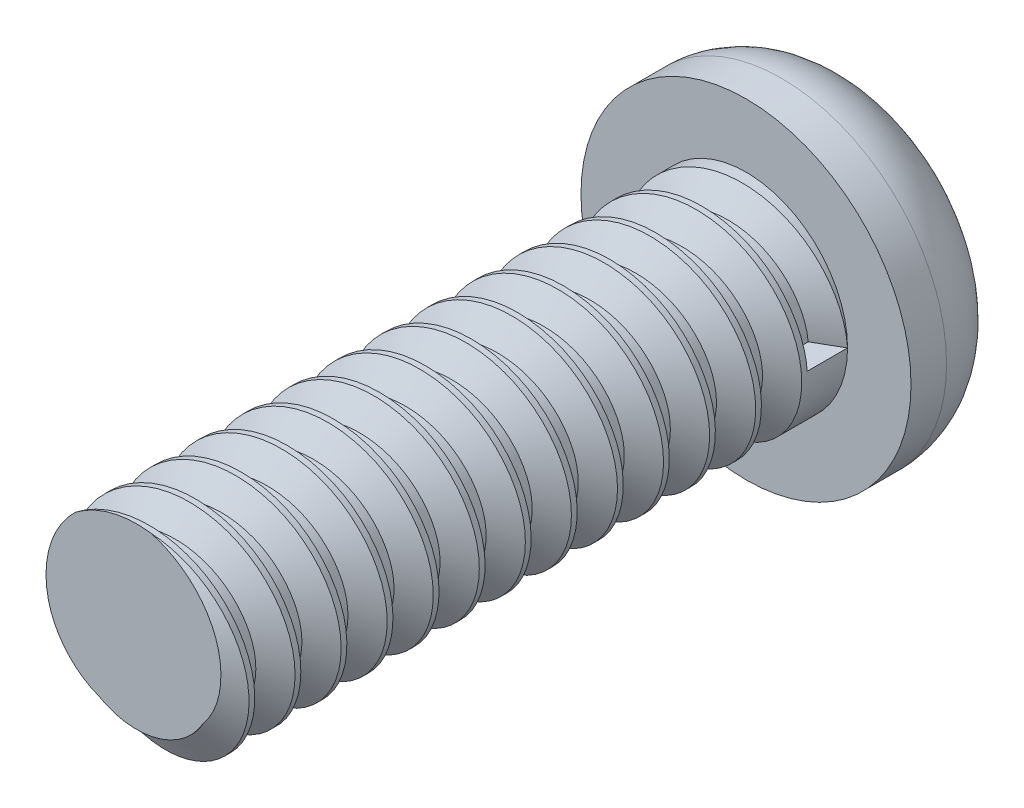
SolidWorks part; units mm, degrees
ref_plane "前视基准面" through (0, 0, 0) normal (0, 0, 1) x (1, 0, 0)
ref_plane "上视基准面" through (0, 0, 0) normal (0, 1, 0) x (1, 0, 0)
ref_plane "右视基准面" through (0, 0, 0) normal (1, 0, 0) x (0, 0, -1)
sketch "草图1" plane through (0, 0, 0) normal (0, 0, 1) x (1, 0, 0)
  circle A0 centre (0, 0) radius 2
extrude "凸台-拉伸1" add sketch "草图1" along normal blind 12
sketch "草图2" plane through (0, 0, 0) normal (0, 0, -1) x (-1, 0, 0)
  circle A0 centre (0, 0) radius 3.25
extrude "凸台-拉伸2" add sketch "草图2" along normal blind 2.2
fillet "圆角1" radius 1.5 1 edges at (-3.25, 0, -2.2)
thread "螺纹线1" pitch 0.9071 method cut profile "螺纹线轮廓1" start angle 0, offset 0, length 0, pitch 0.9071, diameter 4
ref_plane "基准面1" through (2, 0, 0) normal (0, -1, 0) x (1, 0, 0)
sketch "螺纹线轮廓1" plane through (2, 0, 0) normal (0, -1, 0) x (1, 0, 0)
  line L0 (0, 0) -> (0, 0.9071) construction
  line L11 (0, 0) -> (0, 0.7937)
  line L12 (0, 0.7937) -> (-0.491, 0.5103)
  line L13 (-0.491, 0.5103) -> (-0.491, 0.2835)
  line L15 (-0.491, 0.2835) -> (0, 0)
  line L17 (-0.491, 0.3969) -> (0, 0.3969) construction
  point P2 (0, 0)
  dimension "Pitch" = 0.9071
  dimension "Profile_Angle" = 60
  dimension "Profile_Land" = 0.2268
  dimension "Profile_Height" = 0.491
